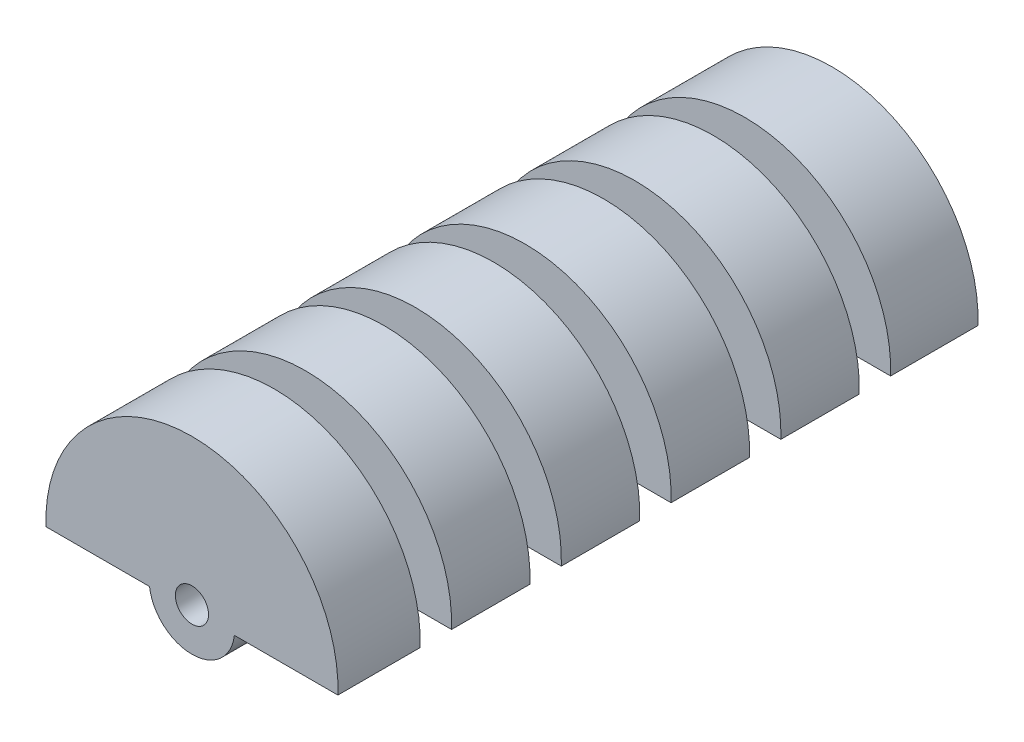
SolidWorks part; units mm, degrees
material "RUBBER 65A Test Modulus"
ref_plane "Front Plane" through (0, 0, 0) normal (0, 0, 1) x (1, 0, 0)
ref_plane "Top Plane" through (0, 0, 0) normal (0, 1, 0) x (1, 0, 0)
ref_plane "Right Plane" through (0, 0, 0) normal (1, 0, 0) x (0, 0, -1)
sketch "Sketch3" plane through (0, 0, 0) normal (0, 0, 1) x (1, 0, 0)
  circle A0 centre (0, 0) radius 27.94
  dimension "D1" = 55.88
extrude "Boss-Extrude2" add sketch "Sketch3" along normal blind 122.46
ref_axis "Axis2" through (0, 0, 121.5887) along (0, 0, -1)
sketch "Sketch5" plane through (0, 0, 122.46) normal (0, 0, 1) x (1, 0, 0)
  circle A0 centre (0, 0) radius 3.175
  dimension "D1" = 6.35
extrude "Cut-Extrude1" cut sketch "Sketch5" against normal through all contours A0
sketch "Sketch4" plane through (0, 0, 0) normal (0, 1, 0) x (1, 0, 0)
  line L0 (0, -122.46) -> (0, 0) construction
  line L1 (-27.94, -122.46) -> (27.94, -122.46) construction
  line L3 (-27.94, -106.72) -> (-13.94, -106.72)
  line L4 (-27.94, -106.72) -> (-27.94, -100.72)
  line L5 (-27.94, -100.72) -> (-13.94, -100.72)
  line L6 (-13.94, -106.72) -> (-13.94, -100.72)
  line L63 (-27.94, -85.72) -> (-27.94, -79.72)
  line L64 (-27.94, -85.72) -> (-13.94, -85.72)
  line L65 (-13.94, -85.72) -> (-13.94, -79.72)
  line L66 (-27.94, -79.72) -> (-13.94, -79.72)
  line L67 (-27.94, -64.72) -> (-27.94, -58.72)
  line L68 (-27.94, -64.72) -> (-13.94, -64.72)
  line L69 (-13.94, -64.72) -> (-13.94, -58.72)
  line L70 (-27.94, -58.72) -> (-13.94, -58.72)
  line L71 (-27.94, -43.72) -> (-27.94, -37.72)
  line L72 (-27.94, -43.72) -> (-13.94, -43.72)
  line L73 (-13.94, -43.72) -> (-13.94, -37.72)
  line L74 (-27.94, -37.72) -> (-13.94, -37.72)
  line L75 (-27.94, -22.72) -> (-27.94, -16.72)
  line L76 (-27.94, -22.72) -> (-13.94, -22.72)
  line L77 (-13.94, -22.72) -> (-13.94, -16.72)
  line L78 (-27.94, -16.72) -> (-13.94, -16.72)
  line L91 (-27.94, -106.72) -> (-27.94, -85.72) construction
  line L92 (-27.94, -1.72) -> (-27.94, 4.28) [skipped]
  line L93 (-27.94, -1.72) -> (-13.94, -1.72) [skipped]
  line L94 (-13.94, -1.72) -> (-13.94, 4.28) [skipped]
  line L95 (-27.94, 4.28) -> (-13.94, 4.28) [skipped]
  line L96 (-27.94, 19.28) -> (-27.94, 25.28) [skipped]
  line L97 (-27.94, 19.28) -> (-13.94, 19.28) [skipped]
  line L98 (-13.94, 19.28) -> (-13.94, 25.28) [skipped]
  line L99 (-27.94, 25.28) -> (-13.94, 25.28) [skipped]
  line L100 (-27.94, 40.28) -> (-27.94, 46.28) [skipped]
  line L101 (-27.94, 40.28) -> (-13.94, 40.28) [skipped]
  line L102 (-13.94, 40.28) -> (-13.94, 46.28) [skipped]
  line L103 (-27.94, 46.28) -> (-13.94, 46.28) [skipped]
  dimension "D1" = 15.74
  dimension "D2" = 6
  dimension "D3" = 27.94
  dimension "D4" = 14
  dimension "D6" = 21
  dimension "D5" = 8
revolve "Cut-Revolve1" cut sketch "Sketch4" angle 360 about L0
shell "Shell1" thickness 3
sketch "Sketch10" plane through (0, 0, 0) normal (0, 0, -1) x (-1, 0, 0)
  line L0 (0, 27.94) -> (0, -27.94) construction
  line L1 (-27.94, 0) -> (27.94, 0) construction
  line L2 (-1, 27.9221) -> (-1, 3.0134)
  line L3 (1, 3.0134) -> (1, 27.9221)
  line L4 (3.0134, 1) -> (27.9221, 1)
  line L5 (3.0134, -1) -> (27.9221, -1)
  line L6 (-1, -3.0134) -> (-1, -27.9221)
  line L7 (1, -3.0134) -> (1, -27.9221)
  line L8 (-27.9221, -1) -> (-3.0134, -1)
  line L9 (-27.9221, 1) -> (-3.0134, 1)
  circle A0 centre (0, 0) radius 27.94 construction
  circle A1 centre (0, 0) radius 3.175 construction
  arc A2 (-1, -27.9221) -> (1, -27.9221) centre (0, 0) ccw
  arc A3 (27.9221, -1) -> (27.9221, 1) centre (0, 0) ccw
  arc A4 (1, 27.9221) -> (-1, 27.9221) centre (0, 0) ccw
  arc A5 (-27.9221, 1) -> (-27.9221, -1) centre (0, 0) ccw
  arc A6 (-1, -3.0134) -> (1, -3.0134) centre (0, 0) ccw
  arc A7 (-3.0134, 1) -> (-3.0134, -1) centre (0, 0) ccw
  arc A8 (1, 3.0134) -> (-1, 3.0134) centre (0, 0) ccw
  arc A9 (3.0134, -1) -> (3.0134, 1) centre (0, 0) ccw
  dimension "D1" = 1
  dimension "D2" = 1
  dimension "D3" = 1
  dimension "D4" = 1
  dimension "D5" = 1
extrude "Boss-Extrude3" add sketch "Sketch10" against normal up to surface (122.46 mm away) up to face at (3.175, 0, 122.46)
ref_plane "Plane1" through (0, 0, 0) normal (-0.7071, -0.7071, 0) x (0, 0, -1)
ref_plane "Plane2" through (0, 0, 0) normal (-0.7071, 0.7071, 0) x (0, 0, -1)
ref_plane "Plane3" through (0, 0, 0) normal (0, 1, 0) x (1, 0, 0)
sketch "Sketch13" plane through (0, 0, 0) normal (0, 1, 0) x (1, 0, 0)
  line L0 (-30.3872, -37.72) -> (-13.9041, -37.72)
  line L1 (-30.3872, -16.72) -> (-13.9041, -16.72)
  line L2 (-30.3872, -16.72) -> (-30.3872, -22.72)
  line L3 (-30.3872, -22.72) -> (-13.9041, -22.72)
  line L4 (-13.9041, -16.72) -> (-13.9041, -22.72)
  line L5 (-30.3872, -37.72) -> (-30.3872, -43.72)
  line L6 (-30.3872, -43.72) -> (-13.9041, -43.72)
  line L7 (-13.9041, -37.72) -> (-13.9041, -43.72)
  line L8 (-30.3872, -58.72) -> (-13.9041, -58.72)
  line L9 (-30.3872, -58.72) -> (-30.3872, -64.72)
  line L10 (-30.3872, -64.72) -> (-13.9041, -64.72)
  line L11 (-13.9041, -58.72) -> (-13.9041, -64.72)
  line L12 (-30.3872, -79.72) -> (-13.9041, -79.72)
  line L13 (-30.3872, -79.72) -> (-30.3872, -85.72)
  line L14 (-30.3872, -85.72) -> (-13.9041, -85.72)
  line L15 (-13.9041, -79.72) -> (-13.9041, -85.72)
  line L16 (-30.3872, -100.72) -> (-13.9041, -100.72)
  line L17 (-30.3872, -100.72) -> (-30.3872, -106.72)
  line L18 (-30.3872, -106.72) -> (-13.9041, -106.72)
  line L19 (-13.9041, -100.72) -> (-13.9041, -106.72)
  dimension "D2" = 6
  dimension "D1" = 5
revolve "Cut-Revolve2" cut sketch "Sketch13" angle 360 about axis through (0, 0, 121.5887) along (0, 0, -1)
sketch "Sketch15" plane through (0, 0, 0) normal (0, 0, -1) x (-1, 0, 0)
  line L0 (0, 0) -> (0, 28.5004) construction
  line L1 (0, 0) -> (-22.0052, 22.0052) construction
sketch "Sketch16" plane through (0, 0, 0) normal (0, 0, -1) x (-1, 0, 0)
  line L0 (-3.175, 0) -> (-6.9755, 0) construction
  line L1 (-27.94, 0) -> (27.94, 0) construction
  line L2 (3.175, 0) -> (7.175, 0) construction
  line L3 (-6.9755, 0) -> (-6.9755, -0.971) construction
  line L4 (-6.9755, -0.971) -> (-6.6911, -0.971) construction
  line L5 (7.175, 0) -> (7.175, -1) construction
  line L8 (-3.175, 0) -> (-6.175, 0) construction
  line L9 (3.175, 0) -> (6.175, 0) construction
  line L10 (-27.9231, -0.971) -> (-6.0982, -0.971)
  line L11 (27.9221, -1) -> (6.0935, -1)
  arc A0 (-27.9231, -0.971) -> (27.9221, -1) centre (0, 0) ccw
  circle A1 centre (0, 0) radius 27.94 construction
  circle A2 centre (0, 0) radius 3.175 construction
  arc A5 (-6.0982, -0.971) -> (6.0935, -1) centre (0, 0) ccw
extrude "Cut-Extrude3" cut sketch "Sketch16" against normal blind 123
sketch "Sketch18" plane through (0, 0, 0) normal (0, 0, -1) x (-1, 0, 0)
  line L0 (-3.175, 0) -> (-8.175, 0)
  line L1 (3.175, 0) -> (8.175, 0)
  line L2 (-6.0982, -0.971) -> (-27.9231, -0.971) construction
  circle A0 centre (0, 0) radius 3.175 construction
  arc A1 (-3.175, 0) -> (3.175, 0) centre (0, 0) ccw
  arc A2 (-8.175, 0) -> (8.175, 0) centre (0, 0) ccw
extrude "Boss-Extrude5" add sketch "Sketch18" against normal blind 122.46
equation "\"inwall\"= .75"
equation "\"outwall\"=2"
